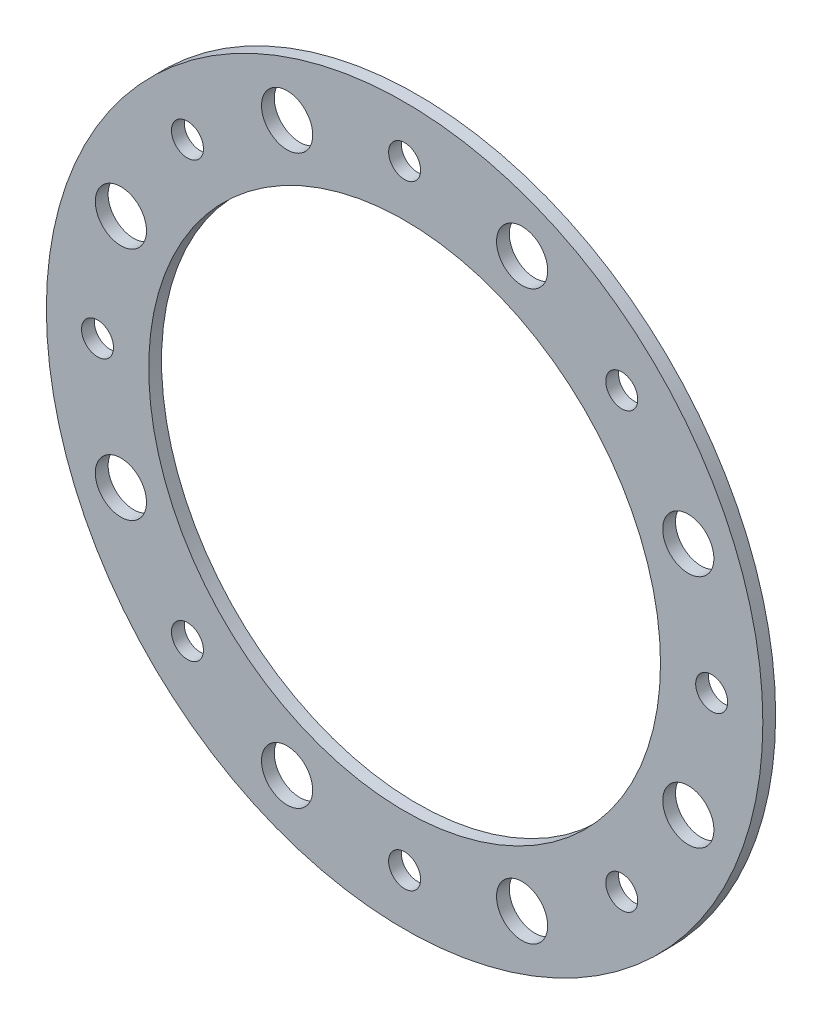
SolidWorks part; units mm, degrees
material "6061-T6 (SS)"
ref_plane "Front Plane" through (0, 0, 0) normal (0, 0, 1) x (1, 0, 0)
ref_plane "Top Plane" through (0, 0, 0) normal (0, 1, 0) x (1, 0, 0)
ref_plane "Right Plane" through (0, 0, 0) normal (1, 0, 0) x (0, 0, -1)
sketch "Sketch1" plane through (0, 0, 0) normal (0, 0, 1) x (1, 0, 0)
  circle A0 centre (0, 0) radius 20
  circle A1 centre (0, 0) radius 28
  dimension "D1" = 40
  dimension "D2" = 56
extrude "Boss-Extrude1" add sketch "Sketch1" along normal blind 1
hole_wizard "Ø2.5 (2.5) Diameter Hole1" positions "Sketch3" profile "Sketch2" hole size "Ø2.5" standard "Ansi Metric"
sketch "Sketch3" plane through (0, 0, 1) normal (0, 0, 1) x (1, 0, 0)
  point P0 (0, 24)
  dimension "D1" = 24
sketch "Sketch2" plane through (0, 24, 1) normal (1, 0, 0) x (0, -1, 0)
  line L0 (0, 0) -> (0, 2.2511)
  line L1 (0, 2.2511) -> (1.25, 1.5)
  line L2 (1.25, 1.5) -> (1.25, 0)
  line L5 (1.25, 0) -> (0, 0)
  line L10 (0, 2.2511) -> (-1.25, 1.5) construction
  line L11 (0, -6.35) -> (0, 107.95) construction
  dimension "Hole Dia." = 2.5
  dimension "Hole Depth" = 1.5
  dimension "Drill Angle" = 118
ref_axis "Axis1" through (0, 0, -0.0127) along (0, 0, -1)
pattern_circular "CirPattern1" count 8 over 360 about axis through (0, 0, -0.0127) along (0, 0, -1) of "Ø2.5 (2.5) Diameter Hole1"
hole_wizard "Ø4.0 (4) Diameter Hole1" positions "Sketch5" profile "Sketch4" hole size "Ø4.0" standard "Ansi Metric"
sketch "Sketch5" plane through (0, 0, 1) normal (0, 0, 1) x (1, 0, 0)
  line L0 (9.1844, 22.1731) -> (0, 0) construction
  line L1 (0, 0) -> (0, 10.7268) construction
  point P0 (9.1844, 22.1731)
  dimension "D1" = 24
  dimension "D2" = 22.5
sketch "Sketch4" plane through (9.1844, 22.1731, 1) normal (1, 0, 0) x (0, -1, 0)
  line L0 (0, 0) -> (0, 2.7017)
  line L1 (0, 2.7017) -> (2, 1.5)
  line L2 (2, 1.5) -> (2, 0)
  line L5 (2, 0) -> (0, 0)
  line L10 (0, 2.7017) -> (-2, 1.5) construction
  line L11 (0, -6.35) -> (0, 107.95) construction
  dimension "Hole Dia." = 4
  dimension "Hole Depth" = 1.5
  dimension "Drill Angle" = 118
pattern_circular "CirPattern2" count 8 over 360 about axis through (0, 0, -0.0127) along (0, 0, -1) of "Ø4.0 (4) Diameter Hole1"
